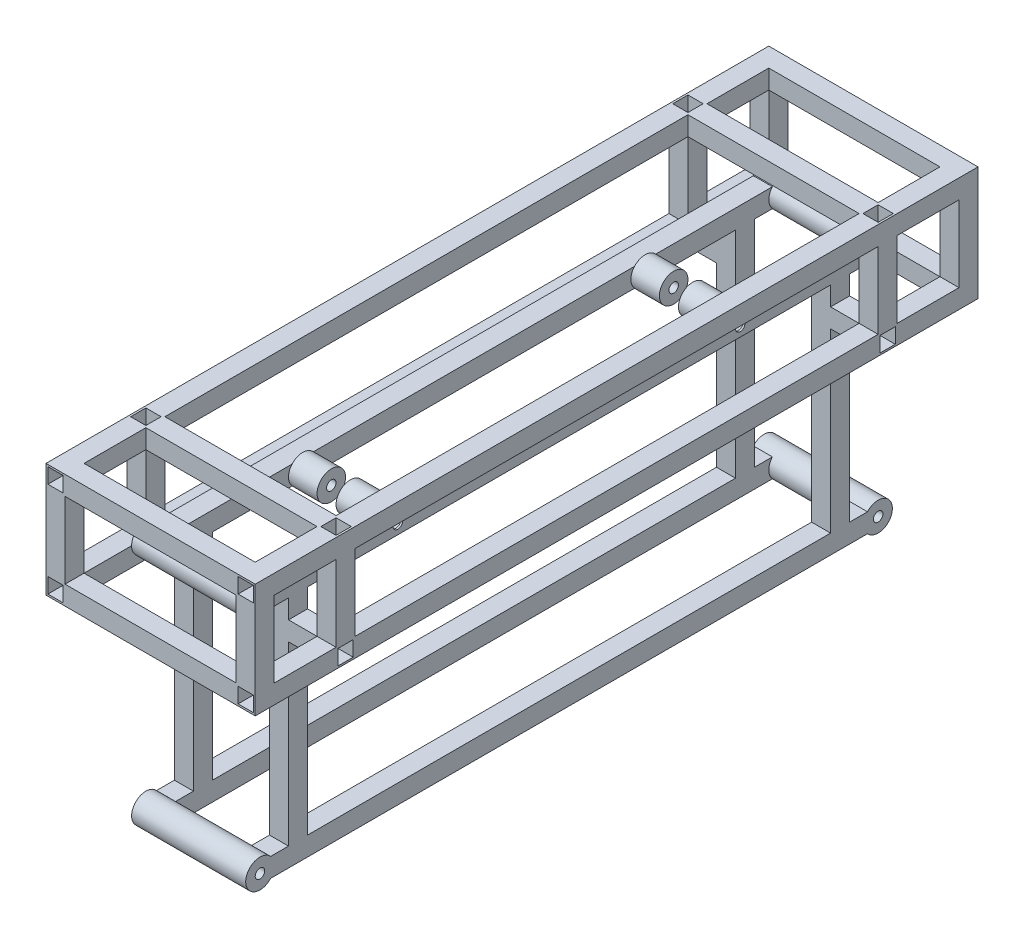
SolidWorks part; units mm, degrees
material "Stop 1060"
ref_plane "Płaszczyzna przednia" through (0, 0, 0) normal (0, 0, 1) x (1, 0, 0)
ref_plane "Płaszczyzna górna" through (0, 0, 0) normal (0, 1, 0) x (1, 0, 0)
ref_plane "Płaszczyzna prawa" through (0, 0, 0) normal (1, 0, 0) x (0, 0, -1)
sketch "Szkic1" plane through (0, 0, 0) normal (0, 0, 1) x (1, 0, 0)
  line L0 (-8, -8) -> (-8, 8)
  line L1 (-10, -10) -> (10, -10)
  line L2 (-10, -10) -> (-10, 10)
  line L3 (-10, 10) -> (10, 10)
  line L4 (10, -10) -> (10, 10)
  line L5 (-10, -10) -> (10, 10) construction
  line L6 (-10, 10) -> (10, -10) construction
  line L7 (-110, -10) -> (-90, -10)
  line L8 (-110, -10) -> (-110, 10)
  line L9 (-110, 10) -> (-90, 10)
  line L10 (-90, -10) -> (-90, 10)
  line L11 (-110, -10) -> (-90, 10) construction
  line L12 (-110, 10) -> (-90, -10) construction
  line L13 (-8, 8) -> (8, 8)
  line L14 (8, -8) -> (8, 8)
  line L15 (-8, -8) -> (8, -8)
  line L16 (-92, -8) -> (-92, 8)
  line L17 (-108, 8) -> (-92, 8)
  line L18 (-108, -8) -> (-108, 8)
  line L19 (-108, -8) -> (-92, -8)
  point P1 (0, 0)
  point P6 (-100, 0)
  dimension "D1" = 20
  dimension "D2" = 20
  dimension "D3" = 100
  dimension "D4" = 20
  dimension "D5" = 20
  dimension "D6" = 2
extrude "Dodanie-wyciągnięcie1" add sketch "Szkic1" along normal mid plane 650
sketch "Szkic3" plane through (10, 0, 0) normal (1, 0, 0) x (0, 0, -1)
  line L0 (-325, -10) -> (-325, 10) construction
  circle A1 centre (-325, 0) radius 15
  dimension "D1" = 30
extrude "Dodanie-wyciągnięcie2" add sketch "Szkic3" against normal blind 120
sketch "Szkic4" plane through (10, 0, 0) normal (1, 0, 0) x (0, 0, -1)
  circle A0 centre (-325, 0) radius 5
  dimension "D1" = 10
extrude "Wytnij-wyciągnięcie1" cut sketch "Szkic4" against normal blind 120
mirror "Lustro1" about plane through (0, 0, 0) normal (0, 0, 1) of "Wytnij-wyciągnięcie1", "Dodanie-wyciągnięcie2"
sketch "Szkic5" plane through (0, 10, 0) normal (0, 1, 0) x (1, 0, 0)
  line L0 (-10, -313.8197) -> (-10, 313.8197) construction
  line L1 (-10, -295) -> (10, -295)
  line L2 (-10, -295) -> (-10, -275)
  line L3 (-10, -275) -> (10, -275)
  line L4 (10, -295) -> (10, -275)
  line L5 (10, -313.8197) -> (10, 313.8197) construction
  line L6 (-110, -313.8197) -> (-110, 313.8197) construction
  line L7 (-110, -295) -> (-90, -295)
  line L8 (-110, -295) -> (-110, -275)
  line L9 (-110, -275) -> (-90, -275)
  line L10 (-90, -295) -> (-90, -275)
  line L11 (-90, -313.8197) -> (-90, 313.8197) construction
  line L16 (-108, -277) -> (-92, -277)
  line L17 (-92, -293) -> (-92, -277)
  line L18 (-108, -293) -> (-92, -293)
  line L19 (-108, -293) -> (-108, -277)
  line L20 (-8, -277) -> (8, -277)
  line L21 (8, -293) -> (8, -277)
  line L22 (-8, -293) -> (8, -293)
  line L23 (-8, -293) -> (-8, -277)
  line L24 (-55, 0) -> (55, 0) construction
  dimension "D1" = 20
  dimension "D2" = 20
  dimension "D5" = 275
  dimension "D6" = 275
  dimension "D3" = 2
  dimension "D4" = 2
extrude "Dodanie-wyciągnięcie3" add sketch "Szkic5" along normal blind 226
mirror "Lustro2" about plane through (0, 0, 0) normal (0, 0, 1) of "Dodanie-wyciągnięcie3"
ref_plane "Płaszczyzna1" through (0, 123, 0) normal (0, 1, 0) x (1, 0, 0)
sketch "Szkic6" plane through (0, 0, 0) normal (0, 0, 1) x (1, 0, 0)
  line L0 (8, 238) -> (8, 254)
  line L1 (-10, 236) -> (10, 236)
  line L2 (-10, 236) -> (-10, 256)
  line L3 (-10, 256) -> (10, 256)
  line L4 (10, 236) -> (10, 256)
  line L5 (-8, 254) -> (8, 254)
  line L6 (-8, 238) -> (-8, 254)
  line L7 (-8, 238) -> (8, 238)
  line L9 (-108, 254) -> (-92, 254)
  line L10 (-110, 236) -> (-90, 236)
  line L11 (-110, 236) -> (-110, 256)
  line L12 (-110, 256) -> (-90, 256)
  line L13 (-90, 236) -> (-90, 256)
  line L14 (-92, 238) -> (-92, 254)
  line L15 (-108, 238) -> (-92, 238)
  line L16 (-108, 238) -> (-108, 254)
  dimension "D1" = 20
  dimension "D3" = 20
  dimension "D4" = 20
  dimension "D2" = 2
  dimension "D5" = 2
extrude "Dodanie-wyciągnięcie4" add sketch "Szkic6" along normal mid plane 650
sketch "Szkic7" plane through (10, 0, 0) normal (1, 0, 0) x (0, 0, -1)
  line L0 (-325, 236) -> (-325, 256) construction
  circle A0 centre (-325, 246) radius 15
  dimension "D1" = 30
extrude "Dodanie-wyciągnięcie5" add sketch "Szkic7" against normal blind 120
sketch "Szkic8" plane through (10, 0, 0) normal (1, 0, 0) x (0, 0, -1)
  circle A0 centre (-325, 246) radius 5
  dimension "D1" = 10
extrude "Wytnij-wyciągnięcie2" cut sketch "Szkic8" against normal blind 120
mirror "Lustro4" about plane through (0, 0, 0) normal (0, 0, 1) of "Dodanie-wyciągnięcie5", "Wytnij-wyciągnięcie2"
sketch "Szkic11" plane through (0, 256, 0) normal (0, 1, 0) x (1, 0, 0)
  line L0 (-10, -313.8197) -> (-10, 313.8197) construction
  line L1 (-60, -300) -> (-40, -300)
  line L2 (-60, -300) -> (-60, 0)
  line L3 (-60, 0) -> (-40, 0)
  line L4 (-40, -300) -> (-40, 0)
  line L5 (-60, -300) -> (-40, 0) construction
  line L6 (-60, 0) -> (-40, -300) construction
  line L7 (-121, 0) -> (121, 0) construction
  point P0 (-50, -150)
  dimension "D1" = 20
  dimension "D2" = 30
  dimension "D3" = 0
  dimension "D4" = 300
sketch "Szkic14" plane through (0, 256, 0) normal (0, 1, 0) x (1, 0, 0)
  line L0 (-110, -313.8197) -> (-110, 313.8197) construction
  line L1 (-60, 0) -> (-40, 0)
  line L2 (-60, 0) -> (-60, 300)
  line L3 (-60, 300) -> (-40, 300)
  line L4 (-40, 0) -> (-40, 300)
  line L5 (-60, 0) -> (-40, 300) construction
  line L6 (-60, 300) -> (-40, 0) construction
  line L7 (-121, 0) -> (121, 0) construction
  point P0 (-50, 150)
  dimension "D1" = 20
  dimension "D2" = 50
  dimension "D3" = 300
  dimension "D4" = 0
sketch "Szkic15" plane through (10, 0, 0) normal (1, 0, 0) x (0, 0, -1)
  line L0 (275, 236) -> (275, 10) construction
  line L1 (275, 216) -> (295, 216)
  line L2 (275, 216) -> (275, 196)
  line L3 (275, 196) -> (295, 196)
  line L4 (295, 216) -> (295, 196)
  line L5 (295, 236) -> (295, 10) construction
  line L7 (-313.8197, 256) -> (313.8197, 256) construction
  line L8 (277, 214) -> (293, 214)
  line L9 (293, 214) -> (293, 198)
  line L10 (277, 198) -> (293, 198)
  line L11 (277, 214) -> (277, 198)
  dimension "D1" = 20
  dimension "D2" = 40
  dimension "D3" = 2
extrude "Dodanie-wyciągnięcie8" add sketch "Szkic15" along normal blind 50
mirror "Lustro5" about plane through (0, 0, 0) normal (0, 0, 1) of "Dodanie-wyciągnięcie8"
sketch "Szkic16" plane through (0, 0, -275) normal (0, 0, 1) x (1, 0, 0)
  line L0 (60, 196) -> (10, 196) construction
  line L1 (60, 216) -> (40, 216)
  line L2 (60, 216) -> (60, 196)
  line L3 (60, 196) -> (40, 196)
  line L4 (40, 216) -> (40, 196)
  line L5 (58, 214) -> (42, 214)
  line L6 (42, 214) -> (42, 198)
  line L7 (58, 198) -> (42, 198)
  line L8 (58, 214) -> (58, 198)
  dimension "D1" = 20
  dimension "D2" = 2
extrude "Dodanie-wyciągnięcie9" add sketch "Szkic16" along normal up to next
ref_plane "Płaszczyzna2" through (-50, 0, 0) normal (1, 0, 0) x (0, 0, -1)
mirror "Lustro6" about plane through (-50, 0, 0) normal (1, 0, 0) of "Dodanie-wyciągnięcie9", "Dodanie-wyciągnięcie8", "Lustro5"
sketch "Szkic17" plane through (0, 216, 0) normal (0, 1, 0) x (1, 0, 0)
  line L0 (58, 293) -> (42, 293)
  line L1 (60, 295) -> (40, 295)
  line L2 (60, 295) -> (60, 275)
  line L3 (60, 275) -> (40, 275)
  line L4 (40, 295) -> (40, 275)
  line L5 (42, 293) -> (42, 277)
  line L6 (58, 277) -> (42, 277)
  line L7 (58, 293) -> (58, 277)
  line L8 (-121, 0) -> (121, 0) construction
  line L9 (40, -295) -> (40, -275)
  line L10 (60, -275) -> (40, -275)
  line L11 (60, -295) -> (60, -275)
  line L12 (58, -293) -> (58, -277)
  line L13 (58, -293) -> (42, -293)
  line L14 (60, -295) -> (40, -295)
  line L15 (42, -293) -> (42, -277)
  line L16 (58, -277) -> (42, -277)
  line L17 (-50, -146.3) -> (-50, 146.3) construction
  line L18 (-158, 293) -> (-158, 277)
  line L19 (-158, 277) -> (-142, 277)
  line L20 (-142, 293) -> (-142, 277)
  line L21 (-140, 295) -> (-140, 275)
  line L22 (-160, 275) -> (-140, 275)
  line L23 (-160, 295) -> (-160, 275)
  line L24 (-160, 295) -> (-140, 295)
  line L25 (-158, 293) -> (-142, 293)
  line L26 (-158, -277) -> (-142, -277)
  line L27 (-142, -293) -> (-142, -277)
  line L28 (-160, -295) -> (-140, -295)
  line L29 (-158, -293) -> (-142, -293)
  line L30 (-158, -293) -> (-158, -277)
  line L31 (-160, -295) -> (-160, -275)
  line L32 (-160, -275) -> (-140, -275)
  line L33 (-140, -295) -> (-140, -275)
  dimension "D1" = 2
extrude "Dodanie-wyciągnięcie10" add sketch "Szkic17" along normal blind 100
ref_plane "Płaszczyzna3" through (0, 0, 380) normal (0, 0, 1) x (1, 0, 0)
sketch "Szkic19" plane through (0, 0, 275) normal (0, 0, -1) x (-1, 0, 0)
  line L0 (160, 196) -> (160, 316) construction
  line L1 (140, 316) -> (160, 316)
  line L2 (140, 316) -> (140, 296)
  line L3 (140, 296) -> (160, 296)
  line L4 (160, 316) -> (160, 296)
  line L5 (142, 314) -> (158, 314)
  line L6 (158, 314) -> (158, 298)
  line L7 (142, 298) -> (158, 298)
  line L8 (142, 314) -> (142, 298)
  dimension "D1" = 20
  dimension "D2" = 2
extrude "Dodanie-wyciągnięcie11" add sketch "Szkic19" along normal up to next
mirror "Lustro7" about plane through (-50, 0, 0) normal (1, 0, 0) of "Dodanie-wyciągnięcie11"
sketch "Szkic20" plane through (-140, 0, 0) normal (1, 0, 0) x (0, 0, -1)
  line L0 (293, 314) -> (293, 298)
  line L1 (295, 316) -> (275, 316)
  line L2 (295, 316) -> (295, 296)
  line L3 (295, 296) -> (275, 296)
  line L4 (275, 316) -> (275, 296)
  line L5 (293, 298) -> (277, 298)
  line L6 (277, 314) -> (277, 298)
  line L7 (293, 314) -> (277, 314)
  dimension "D1" = 2
extrude "Dodanie-wyciągnięcie12" add sketch "Szkic20" along normal up to next
mirror "Lustro8" about plane through (0, 0, 0) normal (0, 0, 1) of "Dodanie-wyciągnięcie12"
sketch "Szkic22" plane through (0, 0, -295) normal (0, 0, -1) x (-1, 0, 0)
  line L0 (-42, 298) -> (-42, 314)
  line L1 (140, 296) -> (160, 296)
  line L2 (140, 296) -> (140, 316)
  line L3 (140, 316) -> (160, 316)
  line L4 (160, 296) -> (160, 316)
  line L5 (140, 216) -> (160, 216)
  line L6 (140, 216) -> (140, 196)
  line L7 (140, 196) -> (160, 196)
  line L8 (160, 216) -> (160, 196)
  line L9 (-40, 216) -> (-60, 216)
  line L10 (-40, 216) -> (-40, 196)
  line L11 (-40, 196) -> (-60, 196)
  line L12 (-60, 216) -> (-60, 196)
  line L13 (-40, 296) -> (-60, 296)
  line L14 (-40, 296) -> (-40, 316)
  line L15 (-40, 316) -> (-60, 316)
  line L16 (-60, 296) -> (-60, 316)
  line L17 (-42, 314) -> (-58, 314)
  line L18 (-58, 298) -> (-58, 314)
  line L19 (-42, 298) -> (-58, 298)
  line L20 (142, 298) -> (158, 298)
  line L21 (158, 298) -> (158, 314)
  line L22 (142, 314) -> (158, 314)
  line L23 (142, 298) -> (142, 314)
  line L24 (142, 214) -> (158, 214)
  line L25 (158, 214) -> (158, 198)
  line L26 (142, 198) -> (158, 198)
  line L27 (142, 214) -> (142, 198)
  line L28 (-42, 214) -> (-58, 214)
  line L29 (-58, 214) -> (-58, 198)
  line L30 (-42, 198) -> (-58, 198)
  line L31 (-42, 214) -> (-42, 198)
  dimension "D1" = 2
extrude "Dodanie-wyciągnięcie13" add sketch "Szkic22" along normal blind 85
sketch "Szkic23" plane through (40, 0, 0) normal (-1, 0, 0) x (0, 0, 1)
  line L0 (295, 196) -> (-380, 196) construction
  line L1 (-380, 216) -> (-360, 216)
  line L2 (-380, 216) -> (-380, 196)
  line L3 (-380, 196) -> (-360, 196)
  line L4 (-360, 216) -> (-360, 196)
  line L5 (-380, 296) -> (-295, 296) construction
  line L6 (-380, 316) -> (-360, 316)
  line L7 (-380, 316) -> (-380, 296)
  line L8 (-380, 296) -> (-360, 296)
  line L9 (-360, 316) -> (-360, 296)
  line L10 (-378, 298) -> (-362, 298)
  line L11 (-362, 314) -> (-362, 298)
  line L12 (-378, 314) -> (-362, 314)
  line L13 (-378, 314) -> (-378, 298)
  line L14 (-378, 214) -> (-362, 214)
  line L15 (-362, 214) -> (-362, 198)
  line L16 (-378, 198) -> (-362, 198)
  line L17 (-378, 214) -> (-378, 198)
  dimension "D1" = 20
  dimension "D2" = 20
  dimension "D3" = 2
extrude "Dodanie-wyciągnięcie14" add sketch "Szkic23" along normal up to next
sketch "Szkic24" plane through (0, 296, 0) normal (0, -1, 0) x (1, 0, 0)
  line L0 (58, -378) -> (58, -362)
  line L1 (-160, -380) -> (-140, -380)
  line L2 (-160, -380) -> (-160, -360)
  line L3 (-160, -360) -> (-140, -360)
  line L4 (-140, -380) -> (-140, -360)
  line L5 (60, -380) -> (40, -380)
  line L6 (60, -380) -> (60, -360)
  line L7 (60, -360) -> (40, -360)
  line L8 (40, -380) -> (40, -360)
  line L9 (58, -362) -> (42, -362)
  line L10 (42, -378) -> (42, -362)
  line L11 (58, -378) -> (42, -378)
  line L12 (-158, -362) -> (-142, -362)
  line L13 (-142, -378) -> (-142, -362)
  line L14 (-158, -378) -> (-142, -378)
  line L15 (-158, -378) -> (-158, -362)
  dimension "D1" = 2
extrude "Dodanie-wyciągnięcie15" add sketch "Szkic24" along normal up to next
mirror "Lustro9" about plane through (0, 0, 0) normal (0, 0, 1) of "Dodanie-wyciągnięcie13", "Dodanie-wyciągnięcie14", "Dodanie-wyciągnięcie15"
sketch "Szkic25" plane through (10, 0, 0) normal (1, 0, 0) x (0, 0, -1)
  line L0 (-275, 236) -> (275, 236) construction
  line L7 (-275, 236) -> (-275, 216) construction
  circle A0 centre (-180, 246) radius 5
  point P6 (-275, 224.5606)
  dimension "D1" = 10
  dimension "D2" = 10
  dimension "D3" = 95
extrude "Wytnij-wyciągnięcie3" cut sketch "Szkic25" against normal blind 120
mirror "Lustro10" about plane through (0, 0, 0) normal (0, 0, 1) of "Wytnij-wyciągnięcie3"
sketch "Szkic26" plane through (-90, 0, 0) normal (1, 0, 0) x (0, 0, -1)
  circle A0 centre (180, 246) radius 15
  circle A1 centre (180, 246) radius 5
  dimension "D1" = 10
  dimension "D2" = 30
extrude "Dodanie-wyciągnięcie16" add sketch "Szkic26" along normal blind 80
mirror "Lustro11" about plane through (0, 0, 0) normal (0, 0, 1) of "Dodanie-wyciągnięcie16"
extrude "Wytnij-wyciągnięcie4" cut sketch "Szkic11" against normal mid plane 80
extrude "Wytnij-wyciągnięcie5" cut sketch "Szkic14" against normal mid plane 80
